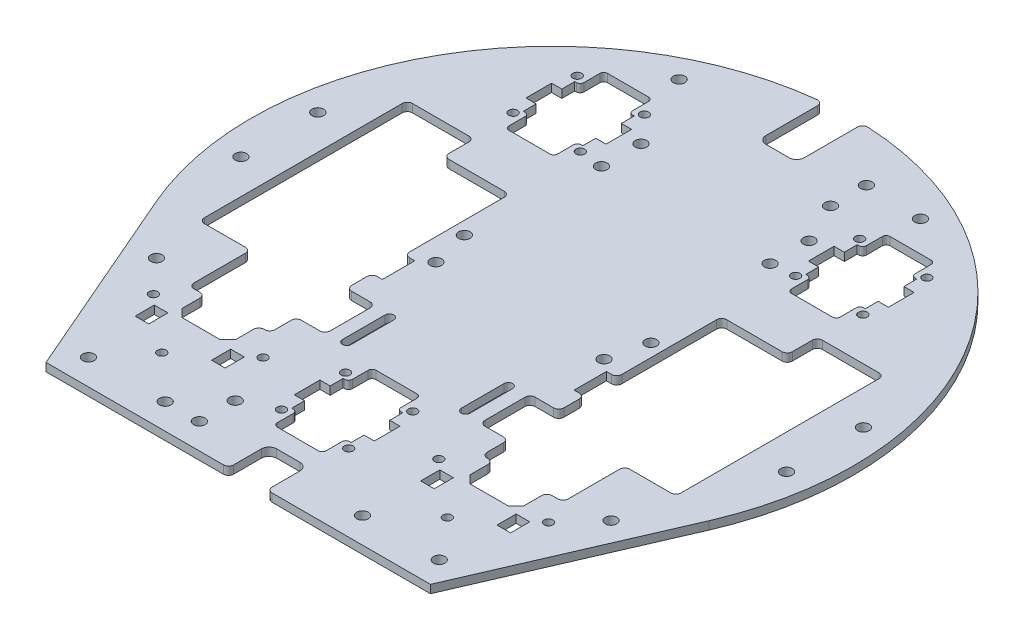
SolidWorks part; units mm, degrees
ref_plane "Front Plane" through (0, 0, 0) normal (0, 0, 1) x (1, 0, 0)
ref_plane "Top Plane" through (0, 0, 0) normal (0, 1, 0) x (1, 0, 0)
ref_plane "Right Plane" through (0, 0, 0) normal (1, 0, 0) x (0, 0, -1)
sketch "Sketch1" plane through (0, 0, 0) normal (0, 1, 0) x (1, 0, 0)
  circle A0 centre (0, 0) radius 117.5
  dimension "D1" = 235
extrude "Boss-Extrude1" add sketch "Sketch1" along normal blind 3.175
sketch "Sketch3" plane through (0, 0, 0) normal (0, 1, 0) x (1, 0, 0)
  line L3 (-107.8261, -46.6881) -> (-75, -122.5)
  line L5 (-75, -122.5) -> (75, -122.5)
  line L6 (75, -122.5) -> (107.8261, -46.6881)
  line L7 (107.8261, -46.6881) -> (-107.8261, -46.6881)
  line L8 (0, -122.5) -> (0, -117.5) construction
  circle A2 centre (0, 0) radius 117.5 construction
  dimension "D1" = 150
  dimension "D2" = 5
extrude "Boss-Extrude2" add sketch "Sketch3" along normal up to surface (3.175 mm away) up to face at (0, 3.175, 117.5)
sketch "Sketch4" plane through (0, 3.175, 0) normal (0, 1, 0) x (1, 0, 0)
  line L0 (70, 31.499) -> (70, -36.6986)
  line L1 (90, 31.499) -> (90, -36.6986)
  line L4 (93, 36.499) -> (67, 36.499)
  line L5 (90, -36.6986) -> (70, -36.6986) construction
  line L6 (67, 36.499) -> (67, 24.7405)
  line L7 (70, 31.499) -> (90, 31.499)
  line L8 (67, 24.7405) -> (41.4, 24.7405)
  line L9 (41.4, 24.7405) -> (41.4, -68.7747)
  line L10 (41.4, -68.7747) -> (73, -68.7747)
  line L11 (73, -68.7747) -> (73, -44.6986)
  line L12 (73, -44.6986) -> (93, -44.6986)
  line L13 (93, -44.6986) -> (93, 36.499)
  line L14 (46.4, 31.499) -> (89.2885, 31.499) construction
  line L15 (70, 31.499) -> (90, 31.499) construction
  line L19 (90, 31.499) -> (90, -36.6986) construction
  line L20 (70, 31.499) -> (70, -36.6986) construction
  line L22 (33.2, -41.8146) -> (33.2, -55.4255)
  line L24 (43.4, -41.8146) -> (33.2, -41.8146)
  line L25 (0, 0) -> (0, 30.6953) construction
  line L26 (-93, -44.6986) -> (-93, 36.499)
  line L27 (-73, -44.6986) -> (-93, -44.6986)
  line L28 (-73, -68.7747) -> (-73, -44.6986)
  line L29 (-41.4, -68.7747) -> (-73, -68.7747)
  line L30 (-41.4, 24.7405) -> (-41.4, -68.7747)
  line L31 (-67, 24.7405) -> (-41.4, 24.7405)
  line L32 (-67, 36.499) -> (-67, 24.7405)
  line L33 (-93, 36.499) -> (-67, 36.499)
  line L35 (33.2, -55.4255) -> (43.4, -55.4255) construction
  line L36 (39.4, -26.8239) -> (39.4, -18.2172)
  line L37 (39.4, -26.8239) -> (43.4, -26.8239)
  line L38 (43.4, -18.2172) -> (39.4, -18.2172)
  line L39 (68, 19.7405) -> (68, -67.7747)
  line L40 (68, -67.7747) -> (43.4, -67.7747)
  line L41 (43.4, 19.7405) -> (68, 19.7405)
  line L42 (43.4, 19.7405) -> (43.4, -18.2172)
  line L43 (43.4, -26.8239) -> (43.4, -41.8146)
  line L44 (43.4, -55.4255) -> (43.4, -67.7747)
  line L45 (43.4, -55.4255) -> (43.4, -67.7747) construction
  line L46 (43.4, -26.8239) -> (43.4, -41.8146) construction
  line L47 (43.4, 19.7405) -> (43.4, -18.2172) construction
  line L48 (43.4, 19.7405) -> (68, 19.7405) construction
  line L49 (68, -67.7747) -> (43.4, -67.7747) construction
  line L50 (68, 19.7405) -> (68, -67.7747) construction
  line L51 (43.4, -18.2172) -> (39.4, -18.2172) construction
  line L52 (39.4, -26.8239) -> (43.4, -26.8239) construction
  line L53 (39.4, -26.8239) -> (39.4, -18.2172) construction
  line L55 (43.4, -41.8146) -> (33.2, -41.8146) construction
  line L56 (33.2, -41.8146) -> (33.2, -55.4255) construction
  line L60 (33.2, -55.4255) -> (43.4, -55.4255)
  line L64 (90, -36.6986) -> (70, -36.6986)
  dimension "D1" = 2
  dimension "D2" = 5
  dimension "D3" = 5
  dimension "D4" = 8
  dimension "D5" = 3
  dimension "D6" = 5
  dimension "D7" = 5
  dimension "D8" = 3
  dimension "D9" = 2
extrude "Cut-Extrude1" cut sketch "Sketch4" against normal through all
sketch "Sketch8" plane through (0, 0, 0) normal (0, -1, 0) x (1, 0, 0)
  line L0 (-42, -78) -> (-68.225, -78) construction
  line L1 (13.1125, 12.5) -> (-13.1125, 12.5)
  line L2 (13.1125, 12.5) -> (13.1125, -12.5)
  line L3 (13.1125, -12.5) -> (-13.1125, -12.5)
  line L4 (-13.1125, 12.5) -> (-13.1125, -12.5)
  line L5 (13.1125, 12.5) -> (-13.1125, -12.5) construction
  line L6 (13.1125, -12.5) -> (-13.1125, 12.5) construction
  line L7 (-42, -53) -> (-42, -78) construction
  line L13 (0, 0) -> (0, -77.7063) construction
  line L14 (0, 80) -> (0, 0) construction
  line L15 (-42, -53) -> (-68.225, -53)
  line L16 (-42, -53) -> (-42, -78)
  line L17 (-42, -78) -> (-68.225, -78)
  line L18 (-68.225, -53) -> (-68.225, -78)
  line L19 (-42, -53) -> (-68.225, -78) construction
  line L20 (-42, -78) -> (-68.225, -53) construction
  line L21 (13.1125, 92.5) -> (-13.1125, 92.5)
  line L22 (13.1125, 92.5) -> (13.1125, 67.5)
  line L23 (13.1125, 67.5) -> (-13.1125, 67.5)
  line L24 (-13.1125, 92.5) -> (-13.1125, 67.5)
  line L25 (13.1125, 92.5) -> (-13.1125, 67.5) construction
  line L26 (13.1125, 67.5) -> (-13.1125, 92.5) construction
  line L27 (-42, -53) -> (-68.225, -53) construction
  line L28 (42, -78) -> (68.225, -78)
  line L29 (68.225, -53) -> (68.225, -78)
  line L30 (42, -78) -> (68.225, -53) construction
  line L31 (42, -53) -> (68.225, -78) construction
  line L32 (42, -53) -> (68.225, -53)
  line L33 (42, -53) -> (42, -78)
  point P0 (0, 0)
  point P15 (-55.1125, -65.5)
  point P20 (0, 80)
  point P29 (55.1125, -65.5)
  dimension "D1" = 42
  dimension "D2" = 80
hole_wizard "M3 Clearance Hole1" positions "Sketch9" profile "Sketch10" hole size "M3" standard "ANSI Metric" end condition through all
sketch "Sketch9" plane through (0, 3.175, 0) normal (0, 1, 0) x (1, 0, 0)
  point P0 (-68.225, 78)
  point P3 (-68.225, 53)
  point P6 (-42, 53)
  point P9 (-42, 78)
  point P12 (42, 78)
  point P15 (68.225, 78)
  point P18 (68.225, 53)
  point P21 (42, 53)
  point P24 (-13.1125, -67.5)
  point P27 (13.1125, -67.5)
  point P30 (13.1125, -92.5)
  point P33 (-13.1125, -92.5)
sketch "Sketch10" plane through (-68.225, 3.175, -78) normal (1, 0, 0) x (0, 0, 1)
  line L0 (0, 0) -> (0, 3.175)
  line L1 (0, 3.175) -> (1.7, 3.175)
  line L2 (1.7, 3.175) -> (1.7, 0)
  line L5 (1.7, 0) -> (0, 0)
  line L11 (0, -6.35) -> (0, 107.95) construction
  dimension "Thru Hole Dia." = 3.4
  dimension "Thru Hole Depth" = 3.175
sketch "Sketch11" plane through (0, 0, 0) normal (0, -1, 0) x (1, 0, 0)
  line L0 (47.6125, -48.2591) -> (62.6125, -48.2591)
  line L1 (62.6125, -82.7409) -> (47.6125, -82.7409)
  line L2 (62.6125, -82.7409) -> (47.6125, -82.7409)
  line L3 (47.6125, -48.2591) -> (62.6125, -48.2591)
  line L4 (-62.6125, -48.2591) -> (-47.6125, -48.2591)
  line L5 (-47.6125, -82.7409) -> (-62.6125, -82.7409)
  line L6 (-47.6125, -82.7409) -> (-62.6125, -82.7409)
  line L7 (-62.6125, -48.2591) -> (-47.6125, -48.2591)
  line L8 (-7.5, 97.2409) -> (7.5, 97.2409)
  line L9 (7.5, 62.7591) -> (-7.5, 62.7591)
  line L10 (7.5, 62.7591) -> (-7.5, 62.7591)
  line L11 (-7.5, 97.2409) -> (7.5, 97.2409)
sketch "Sketch12" plane through (0, 3.175, 0) normal (0, 1, 0) x (1, 0, 0)
  line L1 (-62.6125, 48.2591) -> (-47.6125, 48.2591) construction
  line L2 (-62.6125, 48.2591) -> (-62.6125, 82.7409) construction
  line L3 (-62.6125, 82.7409) -> (-47.6125, 82.7409) construction
  line L4 (-47.6125, 48.2591) -> (-47.6125, 82.7409) construction
  line L5 (47.6125, 48.2591) -> (62.6125, 48.2591) construction
  line L6 (47.6125, 48.2591) -> (47.6125, 82.7409) construction
  line L7 (47.6125, 82.7409) -> (62.6125, 82.7409) construction
  line L8 (62.6125, 48.2591) -> (62.6125, 82.7409) construction
  line L9 (-64.6125, 46.2591) -> (-45.6125, 46.2591)
  line L10 (-7.5, -97.2409) -> (7.5, -97.2409) construction
  line L11 (-7.5, -97.2409) -> (-7.5, -62.7591) construction
  line L12 (-7.5, -62.7591) -> (7.5, -62.7591) construction
  line L13 (7.5, -97.2409) -> (7.5, -62.7591) construction
  line L14 (-45.6125, 46.2591) -> (-45.6125, 84.7409)
  line L15 (-64.6125, 84.7409) -> (-45.6125, 84.7409)
  line L16 (-64.6125, 46.2591) -> (-64.6125, 84.7409)
  line L17 (45.6125, 46.2591) -> (64.6125, 46.2591)
  line L18 (64.6125, 46.2591) -> (64.6125, 84.7409)
  line L19 (45.6125, 84.7409) -> (64.6125, 84.7409)
  line L20 (45.6125, 46.2591) -> (45.6125, 84.7409)
  line L21 (-9.5, -99.2409) -> (9.5, -99.2409)
  line L22 (9.5, -99.2409) -> (9.5, -60.7591)
  line L23 (-9.5, -60.7591) -> (9.5, -60.7591)
  line L24 (-9.5, -99.2409) -> (-9.5, -60.7591)
  dimension "D1" = 2
extrude "Cut-Extrude3" cut sketch "Sketch12" against normal through all
sketch "Sketch13" plane through (0, 0, 0) normal (0, -1, 0) x (1, 0, 0)
  line L0 (-66.225, -75.0394) -> (-63.6125, -75.0394)
  line L1 (-63.6125, -55.9606) -> (-66.225, -55.9606)
  line L2 (-63.6125, -55.9606) -> (-66.225, -55.9606)
  line L3 (-66.225, -75.0394) -> (-63.6125, -75.0394)
  line L4 (-46.6125, -75.0394) -> (-44, -75.0394)
  line L5 (-44, -55.9606) -> (-46.6125, -55.9606)
  line L6 (-44, -55.9606) -> (-46.6125, -55.9606)
  line L7 (-46.6125, -75.0394) -> (-44, -75.0394)
  line L8 (63.6125, -75.0394) -> (66.225, -75.0394)
  line L9 (66.225, -55.9606) -> (63.6125, -55.9606)
  line L10 (66.225, -55.9606) -> (63.6125, -55.9606)
  line L11 (63.6125, -75.0394) -> (66.225, -75.0394)
  line L12 (44, -75.0394) -> (46.6125, -75.0394)
  line L13 (46.6125, -55.9606) -> (44, -55.9606)
  line L14 (46.6125, -55.9606) -> (44, -55.9606)
  line L15 (44, -75.0394) -> (46.6125, -75.0394)
  line L16 (8.5, 70.4606) -> (11.1125, 70.4606)
  line L17 (11.1125, 89.5394) -> (8.5, 89.5394)
  line L18 (11.1125, 89.5394) -> (8.5, 89.5394)
  line L19 (8.5, 70.4606) -> (11.1125, 70.4606)
  line L20 (-11.1125, 70.4606) -> (-8.5, 70.4606)
  line L21 (-8.5, 89.5394) -> (-11.1125, 89.5394)
  line L22 (-8.5, 89.5394) -> (-11.1125, 89.5394)
  line L23 (-11.1125, 70.4606) -> (-8.5, 70.4606)
sketch "Sketch14" plane through (0, 3.175, 0) normal (0, 1, 0) x (1, 0, 0)
  line L0 (-66.725, 55.4606) -> (-43.5, 55.4606)
  line L1 (-66.225, 55.9606) -> (-44, 55.9606) construction
  line L2 (-66.225, 55.9606) -> (-66.225, 75.0394) construction
  line L3 (-66.225, 75.0394) -> (-44, 75.0394) construction
  line L4 (-44, 55.9606) -> (-44, 75.0394) construction
  line L5 (44, 55.9606) -> (66.225, 55.9606) construction
  line L6 (44, 55.9606) -> (44, 75.0394) construction
  line L7 (44, 75.0394) -> (66.225, 75.0394) construction
  line L8 (66.225, 55.9606) -> (66.225, 75.0394) construction
  line L9 (-11.1125, -89.5394) -> (11.1125, -89.5394) construction
  line L10 (-11.1125, -89.5394) -> (-11.1125, -70.4606) construction
  line L11 (-11.1125, -70.4606) -> (11.1125, -70.4606) construction
  line L12 (11.1125, -89.5394) -> (11.1125, -70.4606) construction
  line L13 (-43.5, 55.4606) -> (-43.5, 75.5394)
  line L14 (-66.725, 75.5394) -> (-43.5, 75.5394)
  line L15 (-66.725, 55.4606) -> (-66.725, 75.5394)
  line L16 (43.5, 55.4606) -> (66.725, 55.4606)
  line L17 (66.725, 55.4606) -> (66.725, 75.5394)
  line L18 (43.5, 75.5394) -> (66.725, 75.5394)
  line L19 (43.5, 55.4606) -> (43.5, 75.5394)
  line L20 (-11.6125, -90.0394) -> (11.6125, -90.0394)
  line L21 (11.6125, -90.0394) -> (11.6125, -69.9606)
  line L22 (-11.6125, -69.9606) -> (11.6125, -69.9606)
  line L23 (-11.6125, -90.0394) -> (-11.6125, -69.9606)
  dimension "D1" = 0.5
extrude "Cut-Extrude4" cut sketch "Sketch14" against normal through all
sketch "Sketch15" plane through (0, 3.175, 0) normal (0, 1, 0) x (1, 0, 0)
  line L0 (-66.725, 75.5394) -> (-66.725, 55.4606) construction
  line L1 (-70.725, 60.5) -> (-39.5, 60.5)
  line L2 (-70.725, 60.5) -> (-70.725, 70.5)
  line L3 (-70.725, 70.5) -> (-39.5, 70.5)
  line L4 (-39.5, 60.5) -> (-39.5, 70.5)
  line L5 (-70.725, 60.5) -> (-39.5, 70.5) construction
  line L6 (-70.725, 70.5) -> (-39.5, 60.5) construction
  line L7 (39.5, 60.5) -> (70.725, 60.5)
  line L8 (39.5, 60.5) -> (39.5, 70.5)
  line L9 (39.5, 70.5) -> (70.725, 70.5)
  line L10 (70.725, 60.5) -> (70.725, 70.5)
  line L11 (39.5, 60.5) -> (70.725, 70.5) construction
  line L12 (39.5, 70.5) -> (70.725, 60.5) construction
  line L13 (-15.6125, -85) -> (15.6125, -85)
  line L14 (-15.6125, -85) -> (-15.6125, -75)
  line L15 (-15.6125, -75) -> (15.6125, -75)
  line L16 (15.6125, -85) -> (15.6125, -75)
  line L17 (-15.6125, -85) -> (15.6125, -75) construction
  line L18 (-15.6125, -75) -> (15.6125, -85) construction
  point P0 (-55.1125, 65.5)
  point P5 (55.1125, 65.5)
  point P11 (0, -80)
  dimension "D1" = 4
  dimension "D2" = 10
extrude "Cut-Extrude5" cut sketch "Sketch15" against normal through all
sketch "Sketch16" plane through (0, 0, 0) normal (0, -1, 0) x (1, 0, 0)
  line L4 (-5.225, -101.6482) -> (-2.225, -101.6482) construction
  line L5 (-2.225, -97.6482) -> (-5.225, -97.6482) construction
  line L6 (2.225, 112.6982) -> (5.225, 112.6982) construction
  line L7 (5.225, 116.6982) -> (2.225, 116.6982) construction
  line L8 (-3.775, 122.5) -> (-3.775, 109.6982)
  line L9 (-75, 122.5) -> (75, 122.5) construction
  line L10 (-0.775, 106.6982) -> (8.225, 106.6982)
  line L11 (11.225, 109.6982) -> (11.225, 122.5)
  line L12 (11.225, 122.5) -> (-3.775, 122.5)
  line L13 (3.725, 122.5) -> (3.725, 106.6982) construction
  line L14 (2.225, 114.6982) -> (5.225, 114.6982) construction
  line L15 (-11.225, -116.9626) -> (-11.225, -94.6482)
  line L16 (-8.225, -91.6482) -> (0.775, -91.6482)
  line L17 (3.775, -94.6482) -> (3.775, -117.4393)
  line L18 (-11.225, -94.6482) -> (3.775, -94.6482) construction
  line L19 (-3.725, -91.6482) -> (-3.725, -99.6482) construction
  line L20 (-2.225, -99.6482) -> (-5.225, -99.6482) construction
  arc A4 (-5.225, -97.6482) -> (-5.225, -101.6482) centre (-5.225, -99.6482) ccw construction
  arc A5 (-2.225, -101.6482) -> (-2.225, -97.6482) centre (-2.225, -99.6482) ccw construction
  arc A6 (5.225, 112.6982) -> (5.225, 116.6982) centre (5.225, 114.6982) ccw construction
  arc A7 (2.225, 116.6982) -> (2.225, 112.6982) centre (2.225, 114.6982) ccw construction
  arc A8 (-3.775, 109.6982) -> (-0.775, 106.6982) centre (-0.775, 109.6982) ccw
  arc A9 (8.225, 106.6982) -> (11.225, 109.6982) centre (8.225, 109.6982) ccw
  arc A10 (-107.8261, 46.6881) -> (107.8261, 46.6881) centre (0, 0) ccw construction
  arc A11 (-11.225, -94.6482) -> (-8.225, -91.6482) centre (-8.225, -94.6482) cw
  arc A12 (0.775, -91.6482) -> (3.775, -94.6482) centre (0.775, -94.6482) cw
  arc A13 (-11.225, -116.9626) -> (3.775, -117.4393) centre (0, 0) ccw
  point P26 (3.725, 114.6982)
  point P37 (-3.725, -99.6482)
  dimension "D1" = 8
  dimension "D3" = 3
  dimension "D4" = 8
  dimension "D2" = 15
extrude "Cut-Extrude6" cut sketch "Sketch16" against normal through all
fillet "Fillet1" radius 2 4 edges at (3.775, 1.5875, -117.4393) (-11.225, 1.5875, -116.9626) (11.225, 1.5875, 122.5) (-3.775, 1.5875, 122.5)
hole_wizard "#8 Clearance Hole1" positions "Sketch17" profile "Sketch18" hole size "#8" standard "ANSI Inch" end condition through all
sketch "Sketch17" plane through (0, 0, 0) normal (0, 1, 0) x (1, 0, 0)
  circle A0 centre (-88.6902, -65.7156) radius 1.7272 construction
  circle A1 centre (-106.4483, -15) radius 1.7272 construction
  circle A2 centre (-106.4483, 15) radius 1.7272 construction
  circle A3 centre (32.8, 67.45) radius 1.7272 construction
  circle A4 centre (32.9, 52.1319) radius 1.7272 construction
  circle A5 centre (36.4, 2.1319) radius 1.7272 construction
  circle A6 centre (32.8, -12.55) radius 1.7272 construction
  circle A7 centre (-32.8, -12.55) radius 1.7272 construction
  circle A8 centre (-36.4, 2.1319) radius 1.7272 construction
  circle A9 centre (-32.9, 52.1319) radius 1.7272 construction
  circle A10 centre (-32.8, 67.45) radius 1.7272 construction
  circle A11 centre (-47.0917, 96.6365) radius 1.7272 construction
  circle A12 centre (47.0917, 96.6365) radius 1.7272 construction
  circle A13 centre (106.4483, 15) radius 1.7272 construction
  circle A14 centre (106.4483, -15) radius 1.7272 construction
  circle A15 centre (88.6902, -65.7156) radius 1.7272 construction
  circle A16 centre (38.5, -112.5) radius 1.7272 construction
  circle A19 centre (-38.5, -112.5) radius 1.7272 construction
  circle A20 centre (-68.4328, -112.5) radius 1.7272 construction
  circle A21 centre (-88.6902, -65.7156) radius 1.7272
  circle A22 centre (-106.4483, -15) radius 1.7272
  circle A23 centre (-106.4483, 15) radius 1.7272
  circle A24 centre (32.8, 67.45) radius 1.7272
  circle A25 centre (32.9, 52.1319) radius 1.7272
  circle A26 centre (36.4, 2.1319) radius 1.7272
  circle A27 centre (32.8, -12.55) radius 1.7272
  circle A28 centre (-32.8, -12.55) radius 1.7272
  circle A29 centre (-36.4, 2.1319) radius 1.7272
  circle A30 centre (-32.9, 52.1319) radius 1.7272
  circle A31 centre (-32.8, 67.45) radius 1.7272
  circle A32 centre (-47.0917, 96.6365) radius 1.7272
  circle A33 centre (47.0917, 96.6365) radius 1.7272
  circle A34 centre (106.4483, 15) radius 1.7272
  circle A35 centre (106.4483, -15) radius 1.7272
  circle A36 centre (88.6902, -65.7156) radius 1.7272
  circle A37 centre (38.5, -112.5) radius 1.7272
  circle A38 centre (-25.1638, -98.5) radius 1.7272
  circle A39 centre (-25.1638, -112.5) radius 1.7272
  circle A40 centre (-38.5, -112.5) radius 1.7272
  circle A41 centre (-68.4328, -112.5) radius 1.7272
  circle A42 centre (68.4328, -112.5) radius 1.7272 construction
  circle A43 centre (68.4328, -112.5) radius 1.7272
  circle A45 centre (25.1638, 83.45) radius 1.7272
  circle A47 centre (25.1638, 97.45) radius 1.7272
  circle A48 centre (25.1638, 83.45) radius 1.7272 construction
  circle A50 centre (-25.1638, -98.5) radius 1.7272 construction
  circle A51 centre (-25.1638, -112.5) radius 1.7272 construction
  circle A52 centre (25.1638, 97.45) radius 1.7272 construction
  point P1 (-88.6902, -65.7156)
  point P3 (-106.4483, -15)
  point P5 (-106.4483, 15)
  point P7 (32.8, 67.45)
  point P9 (32.9, 52.1319)
  point P11 (36.4, 2.1319)
  point P13 (32.8, -12.55)
  point P15 (-32.8, -12.55)
  point P17 (-36.4, 2.1319)
  point P19 (-32.9, 52.1319)
  point P21 (-32.8, 67.45)
  point P23 (-47.0917, 96.6365)
  point P25 (47.0917, 96.6365)
  point P27 (106.4483, 15)
  point P29 (106.4483, -15)
  point P31 (88.6902, -65.7156)
  point P33 (38.5, -112.5)
  point P35 (-25.1638, -98.5)
  point P37 (-25.1638, -112.5)
  point P39 (-38.5, -112.5)
  point P41 (-68.4328, -112.5)
  point P109 (68.4328, -112.5)
  point P116 (25.1638, 83.45)
  point P119 (25.1638, 97.45)
sketch "Sketch18" plane through (-88.6902, 0, 65.7156) normal (1, 0, 0) x (0, 0, -1)
  line L0 (0, 0) -> (0, 3.175)
  line L1 (0, 3.175) -> (2.2479, 3.175)
  line L2 (2.2479, 3.175) -> (2.2479, 0)
  line L5 (2.2479, 0) -> (0, 0)
  line L11 (0, -6.35) -> (0, 107.95) construction
  dimension "Thru Hole Dia." = 4.4958
  dimension "Thru Hole Depth" = 3.175
hole_wizard "M3 Clearance Hole2" positions "Sketch19" profile "Sketch20" hole size "M3" standard "ANSI Metric" end condition through all
sketch "Sketch19" plane through (0, 0, 0) normal (0, -1, 0) x (-1, 0, 0)
  circle A1 centre (77.1, -78.5087) radius 1.8
  circle A2 centre (-77.1, -78.5087) radius 1.8 construction
  circle A3 centre (-55.7, -96.6207) radius 1.8 construction
  circle A4 centre (-34.3, -78.5087) radius 1.8 construction
  circle A7 centre (-77.1, -78.5087) radius 1.8
  circle A8 centre (-55.7, -96.6207) radius 1.8
  circle A9 centre (-34.3, -78.5087) radius 1.8
  circle A10 centre (34.3, -78.5087) radius 1.8
  circle A11 centre (55.7, -96.6207) radius 1.8
  circle A12 centre (55.7, -96.6207) radius 1.8 construction
  circle A13 centre (77.1, -78.5087) radius 1.8 construction
  circle A14 centre (34.3, -78.5087) radius 1.8 construction
  point P1 (77.1, -78.5087)
  point P4 (-77.1, -78.5087)
  point P6 (-55.7, -96.6207)
  point P8 (-34.3, -78.5087)
  point P10 (34.3, -78.5087)
  point P12 (55.7, -96.6207)
sketch "Sketch20" plane through (-77.1, 0, 78.5087) normal (1, 0, 0) x (0, 0, -1)
  line L0 (0, 0) -> (0, 3.175)
  line L1 (0, 3.175) -> (1.7, 3.175)
  line L2 (1.7, 3.175) -> (1.7, 0)
  line L5 (1.7, 0) -> (0, 0)
  line L11 (0, -6.35) -> (0, 107.95) construction
  dimension "Thru Hole Dia." = 3.4
  dimension "Thru Hole Depth" = 3.175
sketch "Sketch22" plane through (0, 0, 0) normal (0, -1, 0) x (1, 0, 0)
  line L11 (64.7, 72.5637) -> (64.7, 76.0717) construction
  line L12 (55.319, 78.8177) -> (50.7, 78.8177) construction
  line L13 (47.7, 76.7927) -> (47.7, 71.8427) construction
  line L14 (64.7, 72.5637) -> (64.7, 76.0717) construction
  line L15 (55.319, 78.8177) -> (50.7, 78.8177) construction
  line L16 (47.7, 76.7927) -> (47.7, 71.8427) construction
  line L17 (41.4, 68.7747) -> (73, 68.7747) construction
  line L18 (47.7, 68.7747) -> (64.7, 68.7747) construction
  line L19 (47.7, 68.7747) -> (47.7, 78.8177) construction
  line L20 (47.7, 78.8177) -> (64.7, 78.8177) construction
  line L21 (64.7, 68.7747) -> (64.7, 78.8177) construction
  line L22 (45.7, 66.7747) -> (45.7, 77.8177)
  line L23 (48.7, 80.8177) -> (63.7, 80.8177)
  line L24 (66.7, 66.7747) -> (66.7, 77.8177)
  line L25 (45.7, 66.7747) -> (66.7, 66.7747)
  line L26 (45.7, 77.8177) -> (48.7, 80.8177)
  line L27 (63.7, 80.8177) -> (66.7, 77.8177)
  line L28 (45.7, 66.7747) -> (45.7, 80.8177) construction
  line L29 (45.7, 80.8177) -> (66.7, 80.8177) construction
  line L30 (66.7, 66.7747) -> (66.7, 80.8177) construction
  line L31 (45.7, 77.8177) -> (45.7, 80.8177) construction
  line L32 (45.7, 80.8177) -> (48.7, 80.8177) construction
  line L33 (66.7, 77.8177) -> (66.7, 80.8177) construction
  line L34 (66.7, 80.8177) -> (63.7, 80.8177) construction
  line L35 (0, 0) -> (0, 34.6023) construction
  line L36 (-45.7, 66.7747) -> (-66.7, 66.7747)
  line L37 (-45.7, 66.7747) -> (-45.7, 77.8177)
  line L38 (-45.7, 77.8177) -> (-48.7, 80.8177)
  line L39 (-48.7, 80.8177) -> (-63.7, 80.8177)
  line L40 (-63.7, 80.8177) -> (-66.7, 77.8177)
  line L41 (-66.7, 66.7747) -> (-66.7, 77.8177)
  dimension "D1" = 2
  dimension "D2" = 3
extrude "Cut-Extrude8" cut sketch "Sketch22" against normal through all
fillet "Fillet4" radius 1.5 24 edges at (45.6125, 1.5875, -75.5394) (64.6125, 1.5875, -75.5394) (64.6125, 1.5875, -55.4606) (45.6125, 1.5875, -55.4606) (64.6125, 1.5875, -46.2591) (64.6125, 1.5875, -84.7409) (45.6125, 1.5875, -84.7409) (45.6125, 1.5875, -46.2591) (-64.6125, 1.5875, -46.2591) (-45.6125, 1.5875, -46.2591) (-45.6125, 1.5875, -84.7409) (-64.6125, 1.5875, -84.7409) (-64.6125, 1.5875, -75.5394) (-64.6125, 1.5875, -55.4606) (-45.6125, 1.5875, -55.4606) (-45.6125, 1.5875, -75.5394) (-9.5, 1.5875, 69.9606) (-9.5, 1.5875, 60.7591) (9.5, 1.5875, 60.7591) (9.5, 1.5875, 69.9606) (9.5, 1.5875, 90.0394) (-9.5, 1.5875, 99.2409) (9.5, 1.5875, 99.2409) (-9.5, 1.5875, 90.0394)
sketch "Sketch29" plane through (0, 3.175, 0) normal (0, 1, 0) x (1, 0, 0)
  line L14 (43.4, -28.8239) -> (43.4, -16.2172)
  line L17 (37.4, -28.8239) -> (43.4, -28.8239)
  line L18 (37.4, -16.2172) -> (37.4, -28.8239)
  line L19 (43.4, -16.2172) -> (37.4, -16.2172)
  line L20 (37.4, -28.8239) -> (43.4, -28.8239)
  line L21 (37.4, -16.2172) -> (37.4, -28.8239)
  line L22 (43.4, -16.2172) -> (37.4, -16.2172)
  line L28 (0, 0) -> (0, -34.7576) construction
  line L40 (-37.4, -16.2172) -> (-37.4, -28.8239)
  line L41 (-43.4, -16.2172) -> (-37.4, -16.2172)
  line L42 (-43.4, -28.8239) -> (-43.4, -16.2172)
  line L43 (-37.4, -28.8239) -> (-43.4, -28.8239)
  line L47 (43.4, -38.8146) -> (43.4, -58.4255)
  line L48 (-43.4, -38.8146) -> (-30.2, -38.8146)
  line L49 (-30.2, -38.8146) -> (-30.2, -58.4255)
  line L50 (30.2, -58.4255) -> (43.4, -58.4255)
  line L51 (30.2, -38.8146) -> (30.2, -58.4255)
  line L52 (43.4, -38.8146) -> (30.2, -38.8146)
  line L53 (30.2, -58.4255) -> (43.4, -58.4255)
  line L54 (30.2, -38.8146) -> (30.2, -58.4255)
  line L55 (43.4, -38.8146) -> (30.2, -38.8146)
  line L56 (-30.2, -58.4255) -> (-43.4, -58.4255)
  line L57 (-43.4, -38.8146) -> (-43.4, -58.4255)
  dimension "D2" = 3
  dimension "D1" = 2
extrude "Cut-Extrude9" cut sketch "Sketch29" against normal through all
fillet "Fillet5" radius 2 16 edges at (30.2, 1.5875, 38.8146) (30.2, 1.5875, 58.4255) (41.4, 1.5875, 58.4255) (41.4, 1.5875, 38.8146) (41.4, 1.5875, 28.8239) (41.4, 1.5875, 16.2172) (41.4, 1.5875, -24.7405) (67, 1.5875, -24.7405) (67, 1.5875, -36.499) (93, 1.5875, -36.499) (93, 1.5875, 44.6986) (73, 1.5875, 44.6986) (73, 1.5875, 68.7747) (66.7, 1.5875, 68.7747) (41.4, 1.5875, 68.7747) (45.7, 1.5875, 68.7747)
fillet "Fillet6" radius 2 16 edges at (-41.4, 1.5875, 28.8239) (-41.4, 1.5875, 38.8146) (-30.2, 1.5875, 38.8146) (-30.2, 1.5875, 58.4255) (-41.4, 1.5875, 58.4255) (-73, 1.5875, 68.7747) (-73, 1.5875, 44.6986) (-93, 1.5875, 44.6986) (-67, 1.5875, -36.499) (-67, 1.5875, -24.7405) (-41.4, 1.5875, -24.7405) (-41.4, 1.5875, 16.2172) (-93, 1.5875, -36.499) (-45.7, 1.5875, 68.7747) (-41.4, 1.5875, 68.7747) (-66.7, 1.5875, 68.7747)
sketch "Sketch30" plane through (0, 0, 0) normal (0, -1, 0) x (1, 0, 0)
  line L0 (-73.1, 89.3177) -> (-73.1, 82.1333) construction
  line L1 (-73.1, 82.1333) -> (-68.1, 82.1333) construction
  line L2 (-68.1, 82.1333) -> (-68.1, 89.3177) construction
  line L3 (-68.1, 89.3177) -> (-73.1, 89.3177) construction
  line L4 (-38.3, 82.1333) -> (-38.3, 89.3177) construction
  line L5 (-38.3, 89.3177) -> (-43.3, 89.3177) construction
  line L6 (-43.3, 89.3177) -> (-43.3, 82.1333) construction
  line L7 (-43.3, 82.1333) -> (-38.3, 82.1333) construction
  line L8 (38.3, 89.3177) -> (38.3, 82.1333) construction
  line L9 (38.3, 82.1333) -> (43.3, 82.1333) construction
  line L10 (43.3, 82.1333) -> (43.3, 89.3177) construction
  line L11 (43.3, 89.3177) -> (38.3, 89.3177) construction
  line L12 (73.1, 82.1333) -> (73.1, 89.3177) construction
  line L13 (73.1, 89.3177) -> (68.1, 89.3177) construction
  line L14 (68.1, 89.3177) -> (68.1, 82.1333) construction
  line L15 (68.1, 82.1333) -> (73.1, 82.1333) construction
  line L16 (-73.1, 89.3177) -> (-73.1, 82.1333) construction
  line L17 (-73.1, 82.1333) -> (-68.1, 82.1333) construction
  line L18 (-68.1, 82.1333) -> (-68.1, 89.3177) construction
  line L19 (-68.1, 89.3177) -> (-73.1, 89.3177) construction
  line L20 (-38.3, 82.1333) -> (-38.3, 89.3177) construction
  line L21 (-38.3, 89.3177) -> (-43.3, 89.3177) construction
  line L22 (-43.3, 89.3177) -> (-43.3, 82.1333) construction
  line L23 (-43.3, 82.1333) -> (-38.3, 82.1333) construction
  line L24 (38.3, 89.3177) -> (38.3, 82.1333) construction
  line L25 (38.3, 82.1333) -> (43.3, 82.1333) construction
  line L26 (43.3, 82.1333) -> (43.3, 89.3177) construction
  line L27 (43.3, 89.3177) -> (38.3, 89.3177) construction
  line L28 (73.1, 82.1333) -> (73.1, 89.3177) construction
  line L29 (73.1, 89.3177) -> (68.1, 89.3177) construction
  line L30 (68.1, 89.3177) -> (68.1, 82.1333) construction
  line L31 (68.1, 82.1333) -> (73.1, 82.1333) construction
  line L32 (-73.25, 89.4677) -> (-73.25, 81.9833)
  line L33 (-73.25, 81.9833) -> (-67.95, 81.9833)
  line L34 (-67.95, 81.9833) -> (-67.95, 89.4677)
  line L35 (-67.95, 89.4677) -> (-73.25, 89.4677)
  line L36 (-38.15, 81.9833) -> (-38.15, 89.4677)
  line L37 (-38.15, 89.4677) -> (-43.45, 89.4677)
  line L38 (-43.45, 89.4677) -> (-43.45, 81.9833)
  line L39 (-43.45, 81.9833) -> (-38.15, 81.9833)
  line L40 (38.15, 89.4677) -> (38.15, 81.9833)
  line L41 (38.15, 81.9833) -> (43.45, 81.9833)
  line L42 (43.45, 81.9833) -> (43.45, 89.4677)
  line L43 (43.45, 89.4677) -> (38.15, 89.4677)
  line L44 (73.25, 81.9833) -> (73.25, 89.4677)
  line L45 (73.25, 89.4677) -> (67.95, 89.4677)
  line L46 (67.95, 89.4677) -> (67.95, 81.9833)
  line L47 (67.95, 81.9833) -> (73.25, 81.9833)
  dimension "D1" = 0.15
extrude "Cut-Extrude10" cut sketch "Sketch30" against normal through all
hole_wizard "M3 Clearance Slot1" positions "Sketch26" profile "Sketch24" size "M3" standard "ANSI Metric" slot yes end condition through all
sketch "Sketch26" plane through (0, 3.175, 0) normal (0, 1, 0) x (1, 0, 0)
  line L0 (23.2, -58.62) -> (23.2, -38.62) construction
  line L8 (23.2, -48.62) -> (30.2, -48.62)
  line L10 (30.2, -40.8146) -> (30.2, -56.4255) construction
  line L11 (0, 0) -> (0, -34.2526) construction
  point P0 (23.2, -48.62)
  point P35 (-23.2, -48.62)
  dimension "D1" = 20
  dimension "D2" = 7
sketch "Sketch24" plane through (23.2, 3.175, 48.62) normal (1, 0, 0) x (0, 0, 1)
  line L0 (0, 0) -> (0, 3.175)
  line L1 (0, 3.175) -> (1.7, 3.175)
  line L2 (1.7, 3.175) -> (1.7, 0)
  line L5 (1.7, 0) -> (0, 0)
  line L11 (0, -6.35) -> (0, 107.95) construction
  dimension "Thru Hole Dia." = 3.4
  dimension "Thru Hole Depth" = 3.175
